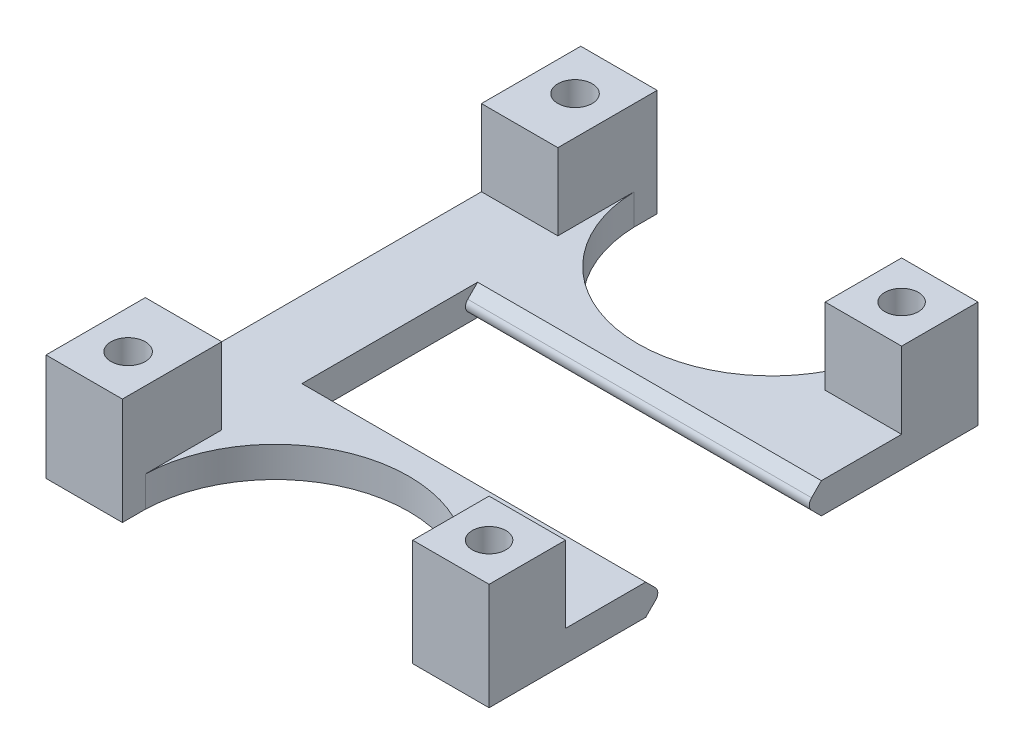
SolidWorks part; units mm, degrees
ref_plane "Front Plane" through (0, 0, 0) normal (0, 0, 1) x (1, 0, 0)
ref_plane "Top Plane" through (0, 0, 0) normal (0, 1, 0) x (1, 0, 0)
ref_plane "Right Plane" through (0, 0, 0) normal (1, 0, 0) x (0, 0, -1)
sketch "Sketch1" plane through (0, 0, 0) normal (0, 1, 0) x (1, 0, 0)
  line L0 (10, 10) -> (10, -10)
  line L2 (0, -20) -> (0, 20)
  line L4 (55, -20) -> (55, 20) construction
  line L5 (10, -10) -> (45, -10)
  line L6 (45, -10) -> (45, 10) construction
  line L7 (45, 10) -> (10, 10)
  line L8 (45, 10) -> (55, 10)
  line L11 (55, 10) -> (55, 20)
  line L13 (27.5, -20) -> (27.5, -10) construction
  line L14 (27.5, 10) -> (27.5, 20) construction
  line L16 (45, -10) -> (55, -10)
  line L17 (55, -20) -> (55, -10)
  line L18 (55, -20) -> (55, -32)
  line L19 (55, -32) -> (45, -32)
  line L20 (0, -32) -> (0, -35)
  line L21 (55, 20) -> (55, 32)
  line L22 (55, 32) -> (45, 32)
  line L23 (0, -35) -> (10, -35)
  line L24 (0, -20) -> (0, -32)
  line L26 (10, -35) -> (10, -32)
  line L27 (0, 20) -> (0, 32)
  line L29 (10, 32) -> (10, 35)
  line L30 (-55, 0) -> (55, 0) construction
  line L31 (0, 0) -> (55, 0) construction
  line L35 (10, 35) -> (0, 35)
  line L36 (0, 35) -> (0, 32)
  arc A26 (45, -32) -> (10, -32) centre (27.5, -32.5074) ccw
  arc A27 (45, 32) -> (10, 32) centre (27.5, 32.5074) cw
  circle A46 centre (50, 27) radius 2.2
  circle A47 centre (50, -27) radius 2.2
  circle A49 centre (5, -29.25) radius 2.2479 construction
  circle A50 centre (5, -29.25) radius 2.2479
  circle A51 centre (5, 29.25) radius 2.2479 construction
  circle A52 centre (5, 29.25) radius 2.2479
  point P30 (27.5, -15)
  point P35 (27.5, 15)
  point P36 (27.5, -10)
  point P39 (0, 0)
  dimension "D18" = 4.4
  dimension "D1" = 40
  dimension "D2" = 55
  dimension "D24" = 10
  dimension "D13" = 5
  dimension "D16" = 5
  dimension "D7" = 10
  dimension "D9" = 5
  dimension "D14" = 5
  dimension "D4" = 20
  dimension "D5" = 10
  dimension "D3" = 10
  dimension "D6" = 35
  dimension "D8" = 12
  dimension "D10" = 10
extrude "Extrude-Body" add sketch "Sketch1" along normal blind 4 contours L4 L2 A47 A46 L7 L6 L5 L0 | L19 L18 A47 | L22 L21 A46 | L27 | L24 region at (9.1098, 0, 0)
sketch "Sketch5" plane through (0, 4, 0) normal (0, 1, 0) x (1, 0, 0)
  line L9 (45, -22) -> (55, -22)
  line L21 (55, -22) -> (55, -32)
  line L23 (0, -35) -> (0, 35) construction
  line L36 (55, -32) -> (45, -32)
  line L37 (45, -32) -> (45, -22)
  line L38 (55, 22) -> (55, 32)
  line L39 (55, 32) -> (45, 32)
  line L41 (45, 32) -> (45, 22)
  line L42 (45, 22) -> (55, 22)
  line L43 (10, 22) -> (10, 35)
  line L45 (10, 35) -> (0, 35)
  line L46 (0, 35) -> (0, 22)
  line L47 (0, -35) -> (0, 35) construction
  line L48 (0, 22) -> (10, 22)
  line L49 (10, -22) -> (0, -22)
  line L50 (0, -22) -> (0, -35)
  line L52 (10, -35) -> (10, -22)
  line L55 (10, -35) -> (0, -35)
  circle A0 centre (50, 27) radius 2.2
  circle A3 centre (50, -27) radius 2.2
  circle A11 centre (50, 27) radius 2.2 construction
  circle A12 centre (50, -27) radius 2.2 construction
  circle A13 centre (5, 29.25) radius 2.2479 construction
  circle A14 centre (5, 29.25) radius 2.2479
  circle A15 centre (5, -29.25) radius 2.2479 construction
  circle A16 centre (5, -29.25) radius 2.2479
  point P3 (0, 34.5742)
  point P22 (0, 0)
  point P24 (0, 0)
  point P25 (10, 34.4944)
  dimension "D1" = 10
  dimension "D2" = 10
  dimension "D3" = 10
  dimension "D4" = 10
  dimension "D5" = 10
  dimension "D6" = 10
  dimension "D8" = 13
extrude "Extrude-Legs" add sketch "Sketch5" along normal blind 10
sketch "Sketch6" plane through (0, 4, 0) normal (0, 1, 0) x (1, 0, 0)
  line L0 (55, -10) -> (55, -22) construction
  line L1 (10, -10) -> (55, -10)
  line L2 (10, -10) -> (10, -9.5)
  line L3 (10, -9.5) -> (55, -9.5)
  line L4 (55, -10) -> (55, -9.5)
  line L5 (10, 10) -> (55, 10)
  line L6 (10, 10) -> (10, 9.5)
  line L7 (10, 9.5) -> (55, 9.5)
  line L8 (55, 10) -> (55, 9.5)
  line L9 (55, 10) -> (55, 22) construction
  dimension "D1" = 19
extrude "Boss-Extrude1" add sketch "Sketch6" against normal up to surface (4 mm away) up to face at (5, 0, -27.0021)
sketch "Sketch7" plane through (55, 0, 0) normal (1, 0, 0) x (0, 0, -1)
  line L0 (-10.2071, 2.7071) -> (-11.5, 4)
  line L1 (-9.5, 0) -> (-9.5, 4) construction
  line L2 (-9.5, 4) -> (-22, 4) construction
  line L3 (-10.2071, 1.2929) -> (-11.5, 0)
  line L4 (-9.5, 0) -> (-32, 0) construction
  line L5 (10.2071, 2.7071) -> (11.5, 4)
  line L6 (9.5, 0) -> (9.5, 4) construction
  line L7 (9.5, 4) -> (22, 4) construction
  line L8 (10.2071, 1.2929) -> (11.5, 0)
  line L9 (9.5, 0) -> (32, 0) construction
  line L10 (11.5, 4) -> (9.5, 4)
  line L11 (9.5, 0) -> (9.5, 4) construction
  line L12 (9.5, 4) -> (9.5, 0)
  line L13 (9.5, 0) -> (11.5, 0)
  line L14 (-11.5, 4) -> (-9.5, 4)
  line L15 (-9.5, 4) -> (-9.5, 0)
  line L16 (-9.5, 0) -> (-11.5, 0)
  line L17 (0, 0) -> (0, 8.2974) construction
  arc A0 (10.2071, 2.7071) -> (10.2071, 1.2929) centre (10.9142, 2) ccw
  arc A1 (-10.2071, 2.7071) -> (-10.2071, 1.2929) centre (-10.9142, 2) cw
  point P36 (9.5, 2)
  point P39 (-9.5, 2)
  dimension "D3" = 1
  dimension "D1" = 45
  dimension "D2" = 45
extrude "Cut-Extrude1" cut sketch "Sketch7" against normal up to surface (45 mm away) up to face at (10, 2, 0)
equation "\"boltdiameter\"=4.4"
equation "\"D18@Sketch1\"=\"boltdiameter\""
equation "\"boltfacediameter\"=7"
equation "\"insetNutFlat\"=8.4"
equation "\"screwInset\"=8.43"
equation "\"slotLength\"=80"
